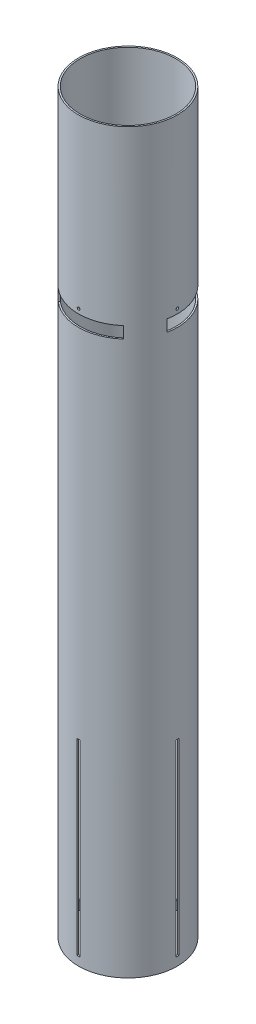
SolidWorks part; units mm, degrees
material "A-Glass Fiber"
ref_plane "Front Plane" through (0, 0, 0) normal (0, 0, 1) x (1, 0, 0)
ref_plane "Top Plane" through (0, 0, 0) normal (0, 1, 0) x (1, 0, 0)
ref_plane "Right Plane" through (0, 0, 0) normal (1, 0, 0) x (0, 0, -1)
sketch "Sketch1" plane through (0, 0, 0) normal (0, 1, 0) x (1, 0, 0)
  circle A0 centre (0, 0) radius 49.53
  circle A1 centre (0, 0) radius 51.1048
  dimension "D1" = 99.06
  dimension "D2" = 102.2096
extrude "Boss-Extrude1" add sketch "Sketch1" along normal blind 762
ref_plane "Plane1" through (0, 0, 0) normal (0.7071, 0, 0.7071) x (0.7071, 0, -0.7071)
ref_axis "Axis1" through (0, 762, 0) along (0, -1, 0)
sketch "Sketch2" plane through (0, 0, 0) normal (1, 0, 0) x (0, 0, -1)
  line L0 (0, 0) -> (0, 8.89)
  line L1 (1.5875, 8.89) -> (-1.5875, 8.89)
  line L2 (1.5875, 8.89) -> (1.5875, 203.2)
  line L3 (1.5875, 203.2) -> (-1.5875, 203.2)
  line L4 (-1.5875, 8.89) -> (-1.5875, 203.2)
  line L5 (1.5875, 8.89) -> (-1.5875, 203.2) construction
  line L6 (1.5875, 203.2) -> (-1.5875, 8.89) construction
  line L7 (51.1048, 762) -> (-51.1048, 762) construction
  line L8 (51.1048, 762) -> (-51.1048, 762)
  line L9 (0, 762) -> (0, 588.645)
  line L10 (-51.1048, 0) -> (51.1048, 0) construction
  circle A0 centre (0, 588.645) radius 1.3525
  point P0 (0, 106.045)
  dimension "D4" = 2.7051
  dimension "D1" = 3.175
  dimension "D2" = 194.31
  dimension "D5" = 588.645
  dimension "D3" = 203.2
extrude "Cut-Extrude1" cut sketch "Sketch2" against normal through all contours L4 L1 L2 L3 region at (0, 106.045, 0)
pattern_circular "CirPattern1" count 4 over 360 about axis through (0, 0, 0) along (0, 1, 0) of "Cut-Extrude1" reverse direction yes
extrude "Cut-Extrude2" cut sketch "Sketch2<3>" against normal through all contours A0 region at (0, 587.7157, 0.9293)
sketch "Sketch2<3>" plane through (0, 0, 0) normal (1, 0, 0) x (0, 0, -1) same geometry as "Sketch2"
pattern_circular "CirPattern2" count 4 over 360 about axis through (0, 762, 0) along (0, -1, 0) of "Cut-Extrude2"
sketch "Sketch3" plane through (0, 0, 0) normal (0.7071, 0, 0.7071) x (0.7071, 0, -0.7071)
  line L0 (0, 0) -> (0, 127) construction
  circle A0 centre (0, 127) radius 3.175
  dimension "D1" = 6.35
  dimension "D2" = 127
extrude "Cut-Extrude3" cut sketch "Sketch3" against normal through all
ref_plane "Plane3" through (0, 583.8825, 0) normal (0, 1, 0) x (1, 0, 0)
sketch "Sketch7" plane through (0, 583.8825, 0) normal (0, 1, 0) x (1, 0, 0)
  line L0 (0, 0) -> (-50.1228, -9.9701)
  line L1 (0, 0) -> (0, 93.232) construction
  line L2 (0, 0) -> (-16.4271, 48.3927)
  line L3 (-51.1048, 0) -> (0, 0) construction
  arc A0 (-51.0869, 1.3526) -> (-51.0869, -1.3525) centre (0, 0) ccw construction
  circle A1 centre (0, 0) radius 49.53 construction
  circle A2 centre (0, 0) radius 51.1048
  circle A3 centre (0, 0) radius 51.1048
  circle A4 centre (0, 0) radius 49.53
  circle A5 centre (0, 0) radius 51.1048 construction
  arc A6 (1.3526, 51.0869) -> (-1.3525, 51.0869) centre (0, 0) ccw construction
  arc A7 (-51.0869, 1.3526) -> (-51.0869, -1.3525) centre (0, 0) ccw
  arc A8 (1.3526, 51.0869) -> (-1.3525, 51.0869) centre (0, 0) ccw
  dimension "D1" = 82.5
  dimension "D3" = 11.25
  dimension "D2" = 0
extrude "Cut-Extrude4" cut sketch "Sketch7" against normal blind 12.065 contours A4 A3 L0 region at (-49.4835, 583.8825, 9.1481)
pattern_circular "CirPattern3" count 3 over 360 about axis through (0, 762, 0) along (0, -1, 0) of "Cut-Extrude4"
equation "\"D1@Boss-Extrude1\" = \"Aft_Section_Length\""
equation "\"AB_Coupler_OD_Length\"= 1in"
equation "\"AB_Coupling_Section_Length\"= 0.375in"
equation "\"AB_Coupler_Length\"= \"AB_Coupler_OD_Length\" + \"AB_Coupling_Section_Length\" * 2"
equation "\"AB_Coupler_Num_Screws\"= 4"
equation "\"AB_Coupling_Screw_Diameter\"= 0.1065in"
equation "\"Aft_Section_Length\"= 30in"
equation "\"D4@Sketch2\"=\"AB_Coupling_Screw_Diameter\""
equation "\"D1@CirPattern2\"=\"AB_Coupler_Num_Screws\""
equation "\"Rail_Nut_From_Bottom\"= 5in"
equation "\"Rail_Nut_Diam\"= 0.25in"
equation "\"D1@Sketch3\"=\"Rail_Nut_Diam\""
equation "\"D2@Sketch3\"=\"Rail_Nut_From_Bottom\""
equation "\"AB_BKHD_Thickness\"= 0.375in"
equation "\"AB_Mount_From_Bottom\"= 23.175in"
equation "\"Cutout_Angle\"= 60"
equation "\"Motor_OD\"= 54mm"
equation "\"Motor_Length\"= 401mm"
equation "\"Mid_Coupler_Length\"= 12in"
equation "\"AB_Paddle_Height\"= 0.375in"
equation "\"Num_Cutouts\"= 4"
equation "\"AB_Coupler_OD\"= 4.024in"
equation "\"AB_Coupler_ID\"= 3.7in"
equation "\"AB_Coupler_Surface_Diameter\"= 3.899in"
equation "\"AB_Central_Bushing_Length\"= 0.75in"
equation "\"Lead_Screw_Dist\"= 2in"
equation "\"Lead_Screw_Diam\"= 0.375in"
equation "\"Lead_Screw_Length\"= \"Mid_Coupler_Length\" + 2*0.375in + 2*0.5in"
equation "\"Paddle_Pin_Offset\"= 0.25in"
equation "\"Paddle_Pin_Radius\"= 2.25*2/3in"
equation "\"Paddle_Gear_OD\"= 3.2in"
equation "\"Fwd_BKHD_From_Top\"= 18in"
equation "\"Body_Tube_OD\"= 4.024in"
equation "\"Body_Tube_ID\"= 3.90in"
equation "\"Coupler_OD\"= 3.899in"
equation "\"Coupler_ID\"= 3.755in"
equation "\"Fwd_Section_Length\"= 25in"
equation "\"Mid_Section_Length\"= 6in"
equation "\"Aft_Upper_Tube_Length\"= 10in"
equation "\"Aft_Lower_Tube_Length\"= 18in"
equation "\"Nosecone_Coupler_Length\"= 5in"
equation "\"Avionics_Bulkhead_Thickness\"= 0.25in"
equation "\"Avionics_Bulkhead_Lip\"= 0.125in"
equation "\"Avionics_Board_Length\"= \"Mid_Coupler_Length\" - 2*\"Avionics_Bulkhead_Lip\""
equation "\"Lead_Screw_Hole_Diam\"= (27/64)*1in"
equation "\"Centering_Ring_Cutout_Dia\"=1.5in"
equation "\"D2@Sketch1\"=\"Body_Tube_OD\""
equation "\"D1@Sketch1\"=\"Body_Tube_ID\""
